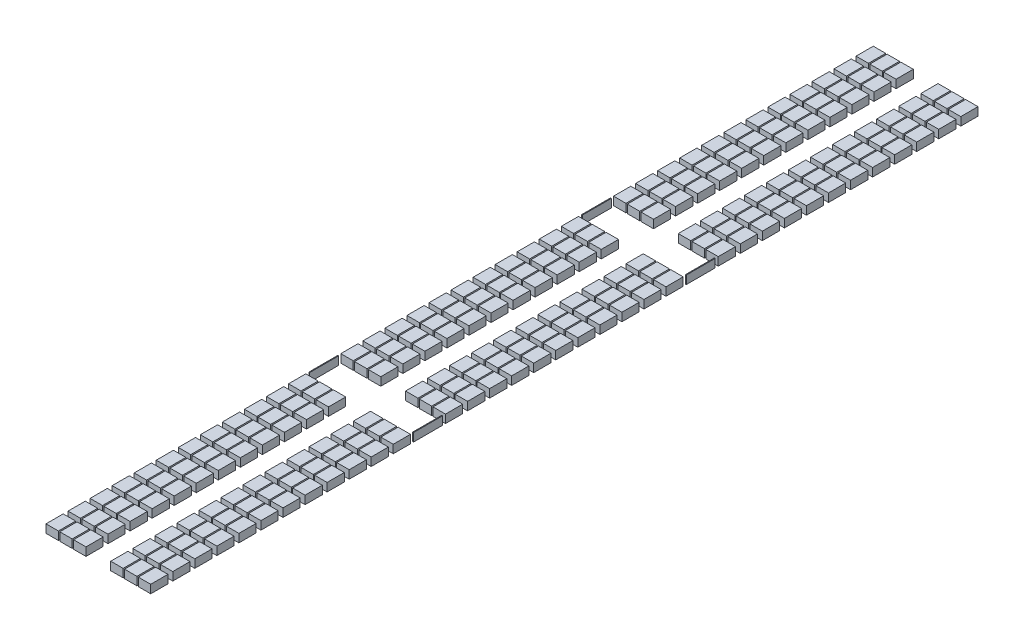
SolidWorks part; units mm, degrees
ref_plane "Front Plane" through (0, 0, 0) normal (0, 0, 1) x (1, 0, 0)
ref_plane "Top Plane" through (0, 0, 0) normal (0, 1, 0) x (1, 0, 0)
ref_plane "Right Plane" through (0, 0, 0) normal (1, 0, 0) x (0, 0, -1)
sketch "Sketch1" plane through (0, 0, 0) normal (0, 1, 0) x (1, 0, 0)
  line L0 (1993.392, 0) -> (-1993.392, 0) construction
  line L1 (1993.392, -15290.8) -> (-1993.392, -15290.8) construction
  line L2 (1993.392, -15290.8) -> (1993.392, 15290.8) construction
  line L3 (1993.392, 15290.8) -> (-1993.392, 15290.8) construction
  line L4 (-1993.392, -15290.8) -> (-1993.392, 15290.8) construction
  line L5 (-1993.392, 5630.3333) -> (1993.392, 5630.3333) construction
  line L6 (-1993.392, 4563.5333) -> (1993.392, 4563.5333) construction
  line L11 (0, -15290.8) -> (0, 15290.8) construction
  line L12 (-1993.392, -4563.5333) -> (1993.392, -4563.5333) construction
  line L13 (-1993.392, -5630.3333) -> (1993.392, -5630.3333) construction
  line L14 (-1421.892, -14613.4667) -> (-964.692, -14613.4667)
  line L15 (-1929.892, -14613.4667) -> (-1472.692, -14613.4667)
  line L16 (-1929.892, -14613.4667) -> (-1929.892, -15248.4667)
  line L17 (-1929.892, -15248.4667) -> (-1472.692, -15248.4667)
  line L18 (-1472.692, -14613.4667) -> (-1472.692, -15248.4667)
  line L19 (-1421.892, -14613.4667) -> (-1421.892, -15248.4667)
  line L20 (-1421.892, -15248.4667) -> (-964.692, -15248.4667)
  line L21 (-964.692, -14613.4667) -> (-964.692, -15248.4667)
  line L22 (-913.892, -14613.4667) -> (-456.692, -14613.4667)
  line L23 (-913.892, -14613.4667) -> (-913.892, -15248.4667)
  line L24 (-913.892, -15248.4667) -> (-456.692, -15248.4667)
  line L25 (-456.692, -14613.4667) -> (-456.692, -15248.4667)
  line L26 (-1421.892, -13800.6667) -> (-964.692, -13800.6667)
  line L27 (-1421.892, -13800.6667) -> (-1421.892, -14435.6667)
  line L28 (-1421.892, -14435.6667) -> (-964.692, -14435.6667)
  line L29 (-964.692, -13800.6667) -> (-964.692, -14435.6667)
  line L30 (-913.892, -13800.6667) -> (-456.692, -13800.6667)
  line L31 (-913.892, -13800.6667) -> (-913.892, -14435.6667)
  line L32 (-913.892, -14435.6667) -> (-456.692, -14435.6667)
  line L33 (-456.692, -13800.6667) -> (-456.692, -14435.6667)
  line L34 (-1421.892, -12987.8667) -> (-964.692, -12987.8667)
  line L35 (-1421.892, -12987.8667) -> (-1421.892, -13622.8667)
  line L36 (-1421.892, -13622.8667) -> (-964.692, -13622.8667)
  line L37 (-964.692, -12987.8667) -> (-964.692, -13622.8667)
  line L38 (-913.892, -12987.8667) -> (-456.692, -12987.8667)
  line L39 (-913.892, -12987.8667) -> (-913.892, -13622.8667)
  line L40 (-913.892, -13622.8667) -> (-456.692, -13622.8667)
  line L41 (-456.692, -12987.8667) -> (-456.692, -13622.8667)
  line L42 (-1929.892, -13800.6667) -> (-1472.692, -13800.6667)
  line L43 (-1929.892, -13800.6667) -> (-1929.892, -14435.6667)
  line L44 (-1929.892, -14435.6667) -> (-1472.692, -14435.6667)
  line L45 (-1472.692, -13800.6667) -> (-1472.692, -14435.6667)
  line L46 (-1929.892, -12987.8667) -> (-1472.692, -12987.8667)
  line L47 (-1929.892, -12987.8667) -> (-1929.892, -13622.8667)
  line L48 (-1929.892, -13622.8667) -> (-1472.692, -13622.8667)
  line L49 (-1472.692, -12987.8667) -> (-1472.692, -13622.8667)
  line L50 (-1929.892, -12175.0667) -> (-1472.692, -12175.0667)
  line L51 (-1929.892, -12175.0667) -> (-1929.892, -12810.0667)
  line L52 (-1929.892, -12810.0667) -> (-1472.692, -12810.0667)
  line L53 (-1472.692, -12175.0667) -> (-1472.692, -12810.0667)
  line L54 (-1421.892, -12175.0667) -> (-964.692, -12175.0667)
  line L55 (-1421.892, -12175.0667) -> (-1421.892, -12810.0667)
  line L56 (-1421.892, -12810.0667) -> (-964.692, -12810.0667)
  line L57 (-964.692, -12175.0667) -> (-964.692, -12810.0667)
  line L58 (-913.892, -12175.0667) -> (-456.692, -12175.0667)
  line L59 (-913.892, -12175.0667) -> (-913.892, -12810.0667)
  line L60 (-913.892, -12810.0667) -> (-456.692, -12810.0667)
  line L61 (-456.692, -12175.0667) -> (-456.692, -12810.0667)
  line L62 (-1929.892, -11362.2667) -> (-1472.692, -11362.2667)
  line L63 (-1929.892, -11362.2667) -> (-1929.892, -11997.2667)
  line L64 (-1929.892, -11997.2667) -> (-1472.692, -11997.2667)
  line L65 (-1472.692, -11362.2667) -> (-1472.692, -11997.2667)
  line L66 (-1421.892, -11362.2667) -> (-964.692, -11362.2667)
  line L67 (-1421.892, -11362.2667) -> (-1421.892, -11997.2667)
  line L68 (-1421.892, -11997.2667) -> (-964.692, -11997.2667)
  line L69 (-964.692, -11362.2667) -> (-964.692, -11997.2667)
  line L70 (-913.892, -11362.2667) -> (-456.692, -11362.2667)
  line L71 (-913.892, -11362.2667) -> (-913.892, -11997.2667)
  line L72 (-913.892, -11997.2667) -> (-456.692, -11997.2667)
  line L73 (-456.692, -11362.2667) -> (-456.692, -11997.2667)
  line L74 (-1929.892, -10549.4667) -> (-1472.692, -10549.4667)
  line L75 (-1929.892, -10549.4667) -> (-1929.892, -11184.4667)
  line L76 (-1929.892, -11184.4667) -> (-1472.692, -11184.4667)
  line L77 (-1472.692, -10549.4667) -> (-1472.692, -11184.4667)
  line L78 (-1421.892, -10549.4667) -> (-964.692, -10549.4667)
  line L79 (-1421.892, -10549.4667) -> (-1421.892, -11184.4667)
  line L80 (-1421.892, -11184.4667) -> (-964.692, -11184.4667)
  line L81 (-964.692, -10549.4667) -> (-964.692, -11184.4667)
  line L82 (-913.892, -10549.4667) -> (-456.692, -10549.4667)
  line L83 (-913.892, -10549.4667) -> (-913.892, -11184.4667)
  line L84 (-913.892, -11184.4667) -> (-456.692, -11184.4667)
  line L85 (-456.692, -10549.4667) -> (-456.692, -11184.4667)
  line L86 (-1929.892, -9736.6667) -> (-1472.692, -9736.6667)
  line L87 (-1929.892, -9736.6667) -> (-1929.892, -10371.6667)
  line L88 (-1929.892, -10371.6667) -> (-1472.692, -10371.6667)
  line L89 (-1472.692, -9736.6667) -> (-1472.692, -10371.6667)
  line L90 (-1421.892, -9736.6667) -> (-964.692, -9736.6667)
  line L91 (-1421.892, -9736.6667) -> (-1421.892, -10371.6667)
  line L92 (-1421.892, -10371.6667) -> (-964.692, -10371.6667)
  line L93 (-964.692, -9736.6667) -> (-964.692, -10371.6667)
  line L94 (-913.892, -9736.6667) -> (-456.692, -9736.6667)
  line L95 (-913.892, -9736.6667) -> (-913.892, -10371.6667)
  line L96 (-913.892, -10371.6667) -> (-456.692, -10371.6667)
  line L97 (-456.692, -9736.6667) -> (-456.692, -10371.6667)
  line L98 (-1929.892, -8923.8667) -> (-1472.692, -8923.8667)
  line L99 (-1929.892, -8923.8667) -> (-1929.892, -9558.8667)
  line L100 (-1929.892, -9558.8667) -> (-1472.692, -9558.8667)
  line L101 (-1472.692, -8923.8667) -> (-1472.692, -9558.8667)
  line L102 (-1421.892, -8923.8667) -> (-964.692, -8923.8667)
  line L103 (-1421.892, -8923.8667) -> (-1421.892, -9558.8667)
  line L104 (-1421.892, -9558.8667) -> (-964.692, -9558.8667)
  line L105 (-964.692, -8923.8667) -> (-964.692, -9558.8667)
  line L106 (-913.892, -8923.8667) -> (-456.692, -8923.8667)
  line L107 (-913.892, -8923.8667) -> (-913.892, -9558.8667)
  line L108 (-913.892, -9558.8667) -> (-456.692, -9558.8667)
  line L109 (-456.692, -8923.8667) -> (-456.692, -9558.8667)
  line L110 (-1929.892, -8111.0667) -> (-1472.692, -8111.0667)
  line L111 (-1929.892, -8111.0667) -> (-1929.892, -8746.0667)
  line L112 (-1929.892, -8746.0667) -> (-1472.692, -8746.0667)
  line L113 (-1472.692, -8111.0667) -> (-1472.692, -8746.0667)
  line L114 (-1421.892, -8111.0667) -> (-964.692, -8111.0667)
  line L115 (-1421.892, -8111.0667) -> (-1421.892, -8746.0667)
  line L116 (-1421.892, -8746.0667) -> (-964.692, -8746.0667)
  line L117 (-964.692, -8111.0667) -> (-964.692, -8746.0667)
  line L118 (-913.892, -8111.0667) -> (-456.692, -8111.0667)
  line L119 (-913.892, -8111.0667) -> (-913.892, -8746.0667)
  line L120 (-913.892, -8746.0667) -> (-456.692, -8746.0667)
  line L121 (-456.692, -8111.0667) -> (-456.692, -8746.0667)
  line L122 (-1929.892, -7298.2667) -> (-1472.692, -7298.2667)
  line L123 (-1929.892, -7298.2667) -> (-1929.892, -7933.2667)
  line L124 (-1929.892, -7933.2667) -> (-1472.692, -7933.2667)
  line L125 (-1472.692, -7298.2667) -> (-1472.692, -7933.2667)
  line L126 (-1421.892, -7298.2667) -> (-964.692, -7298.2667)
  line L127 (-1421.892, -7298.2667) -> (-1421.892, -7933.2667)
  line L128 (-1421.892, -7933.2667) -> (-964.692, -7933.2667)
  line L129 (-964.692, -7298.2667) -> (-964.692, -7933.2667)
  line L130 (-913.892, -7298.2667) -> (-456.692, -7298.2667)
  line L131 (-913.892, -7298.2667) -> (-913.892, -7933.2667)
  line L132 (-913.892, -7933.2667) -> (-456.692, -7933.2667)
  line L133 (-456.692, -7298.2667) -> (-456.692, -7933.2667)
  line L134 (-1929.892, -6485.4667) -> (-1472.692, -6485.4667)
  line L135 (-1929.892, -6485.4667) -> (-1929.892, -7120.4667)
  line L136 (-1929.892, -7120.4667) -> (-1472.692, -7120.4667)
  line L137 (-1472.692, -6485.4667) -> (-1472.692, -7120.4667)
  line L138 (-1421.892, -6485.4667) -> (-964.692, -6485.4667)
  line L139 (-1421.892, -6485.4667) -> (-1421.892, -7120.4667)
  line L140 (-1421.892, -7120.4667) -> (-964.692, -7120.4667)
  line L141 (-964.692, -6485.4667) -> (-964.692, -7120.4667)
  line L142 (-913.892, -6485.4667) -> (-456.692, -6485.4667)
  line L143 (-913.892, -6485.4667) -> (-913.892, -7120.4667)
  line L144 (-913.892, -7120.4667) -> (-456.692, -7120.4667)
  line L145 (-456.692, -6485.4667) -> (-456.692, -7120.4667)
  line L146 (-1929.892, -5672.6667) -> (-1472.692, -5672.6667)
  line L147 (-1929.892, -5672.6667) -> (-1929.892, -6307.6667)
  line L148 (-1929.892, -6307.6667) -> (-1472.692, -6307.6667)
  line L149 (-1472.692, -5672.6667) -> (-1472.692, -6307.6667)
  line L150 (-1421.892, -5672.6667) -> (-964.692, -5672.6667)
  line L151 (-1421.892, -5672.6667) -> (-1421.892, -6307.6667)
  line L152 (-1421.892, -6307.6667) -> (-964.692, -6307.6667)
  line L153 (-964.692, -5672.6667) -> (-964.692, -6307.6667)
  line L154 (-913.892, -5672.6667) -> (-456.692, -5672.6667)
  line L155 (-913.892, -5672.6667) -> (-913.892, -6307.6667)
  line L156 (-913.892, -6307.6667) -> (-456.692, -6307.6667)
  line L157 (-456.692, -5672.6667) -> (-456.692, -6307.6667)
  line L158 (-456.692, -5672.6667) -> (-456.692, -15248.4667) construction
  line L159 (-456.692, -10460.5667) -> (2544.9668, -10460.5667) construction
  line L160 (-1929.892, -3746.5) -> (-1472.692, -3746.5)
  line L161 (-1929.892, -3746.5) -> (-1929.892, -4381.5)
  line L162 (-1929.892, -4381.5) -> (-1472.692, -4381.5)
  line L163 (-1472.692, -3746.5) -> (-1472.692, -4381.5)
  line L164 (-1421.892, -3746.5) -> (-964.692, -3746.5)
  line L165 (-1421.892, -3746.5) -> (-1421.892, -4381.5)
  line L166 (-1421.892, -4381.5) -> (-964.692, -4381.5)
  line L167 (-964.692, -3746.5) -> (-964.692, -4381.5)
  line L168 (-913.892, -3746.5) -> (-456.692, -3746.5)
  line L169 (-913.892, -3746.5) -> (-913.892, -4381.5)
  line L170 (-913.892, -4381.5) -> (-456.692, -4381.5)
  line L171 (-456.692, -3746.5) -> (-456.692, -4381.5)
  line L172 (-1421.892, -2933.7) -> (-964.692, -2933.7)
  line L173 (-1421.892, -2933.7) -> (-1421.892, -3568.7)
  line L174 (-1421.892, -3568.7) -> (-964.692, -3568.7)
  line L175 (-964.692, -2933.7) -> (-964.692, -3568.7)
  line L176 (-913.892, -2933.7) -> (-456.692, -2933.7)
  line L177 (-913.892, -2933.7) -> (-913.892, -3568.7)
  line L178 (-913.892, -3568.7) -> (-456.692, -3568.7)
  line L179 (-456.692, -2933.7) -> (-456.692, -3568.7)
  line L180 (-1421.892, -2120.9) -> (-964.692, -2120.9)
  line L181 (-1421.892, -2120.9) -> (-1421.892, -2755.9)
  line L182 (-1421.892, -2755.9) -> (-964.692, -2755.9)
  line L183 (-964.692, -2120.9) -> (-964.692, -2755.9)
  line L184 (-913.892, -2120.9) -> (-456.692, -2120.9)
  line L185 (-913.892, -2120.9) -> (-913.892, -2755.9)
  line L186 (-913.892, -2755.9) -> (-456.692, -2755.9)
  line L187 (-456.692, -2120.9) -> (-456.692, -2755.9)
  line L188 (-1421.892, -1308.1) -> (-964.692, -1308.1)
  line L189 (-1421.892, -1308.1) -> (-1421.892, -1943.1)
  line L190 (-1421.892, -1943.1) -> (-964.692, -1943.1)
  line L191 (-964.692, -1308.1) -> (-964.692, -1943.1)
  line L192 (-913.892, -1308.1) -> (-456.692, -1308.1)
  line L193 (-913.892, -1308.1) -> (-913.892, -1943.1)
  line L194 (-913.892, -1943.1) -> (-456.692, -1943.1)
  line L195 (-456.692, -1308.1) -> (-456.692, -1943.1)
  line L196 (-1421.892, -495.3) -> (-964.692, -495.3)
  line L197 (-1421.892, -495.3) -> (-1421.892, -1130.3)
  line L198 (-1421.892, -1130.3) -> (-964.692, -1130.3)
  line L199 (-964.692, -495.3) -> (-964.692, -1130.3)
  line L200 (-913.892, -495.3) -> (-456.692, -495.3)
  line L201 (-913.892, -495.3) -> (-913.892, -1130.3)
  line L202 (-913.892, -1130.3) -> (-456.692, -1130.3)
  line L203 (-456.692, -495.3) -> (-456.692, -1130.3)
  line L204 (-1929.892, -2933.7) -> (-1472.692, -2933.7)
  line L205 (-1929.892, -2933.7) -> (-1929.892, -3568.7)
  line L206 (-1929.892, -3568.7) -> (-1472.692, -3568.7)
  line L207 (-1472.692, -2933.7) -> (-1472.692, -3568.7)
  line L208 (-1929.892, -2120.9) -> (-1472.692, -2120.9)
  line L209 (-1929.892, -2120.9) -> (-1929.892, -2755.9)
  line L210 (-1929.892, -2755.9) -> (-1472.692, -2755.9)
  line L211 (-1472.692, -2120.9) -> (-1472.692, -2755.9)
  line L212 (-1929.892, -1308.1) -> (-1472.692, -1308.1)
  line L213 (-1929.892, -1308.1) -> (-1929.892, -1943.1)
  line L214 (-1929.892, -1943.1) -> (-1472.692, -1943.1)
  line L215 (-1472.692, -1308.1) -> (-1472.692, -1943.1)
  line L216 (-1929.892, -495.3) -> (-1472.692, -495.3)
  line L217 (-1929.892, -495.3) -> (-1929.892, -1130.3)
  line L218 (-1929.892, -1130.3) -> (-1472.692, -1130.3)
  line L219 (-1472.692, -495.3) -> (-1472.692, -1130.3)
  line L220 (-1929.892, 317.5) -> (-1472.692, 317.5)
  line L221 (-1929.892, 317.5) -> (-1929.892, -317.5)
  line L222 (-1929.892, -317.5) -> (-1472.692, -317.5)
  line L223 (-1472.692, 317.5) -> (-1472.692, -317.5)
  line L224 (-1421.892, 317.5) -> (-964.692, 317.5)
  line L225 (-1421.892, 317.5) -> (-1421.892, -317.5)
  line L226 (-1421.892, -317.5) -> (-964.692, -317.5)
  line L227 (-964.692, 317.5) -> (-964.692, -317.5)
  line L228 (-913.892, 317.5) -> (-456.692, 317.5)
  line L229 (-913.892, 317.5) -> (-913.892, -317.5)
  line L230 (-913.892, -317.5) -> (-456.692, -317.5)
  line L231 (-456.692, 317.5) -> (-456.692, -317.5)
  line L232 (-1929.892, 1130.3) -> (-1472.692, 1130.3)
  line L233 (-1929.892, 1130.3) -> (-1929.892, 495.3)
  line L234 (-1929.892, 495.3) -> (-1472.692, 495.3)
  line L235 (-1472.692, 1130.3) -> (-1472.692, 495.3)
  line L236 (-1421.892, 1130.3) -> (-964.692, 1130.3)
  line L237 (-1421.892, 1130.3) -> (-1421.892, 495.3)
  line L238 (-1421.892, 495.3) -> (-964.692, 495.3)
  line L239 (-964.692, 1130.3) -> (-964.692, 495.3)
  line L240 (-913.892, 1130.3) -> (-456.692, 1130.3)
  line L241 (-913.892, 1130.3) -> (-913.892, 495.3)
  line L242 (-913.892, 495.3) -> (-456.692, 495.3)
  line L243 (-456.692, 1130.3) -> (-456.692, 495.3)
  line L244 (-1929.892, 1943.1) -> (-1472.692, 1943.1)
  line L245 (-1929.892, 1943.1) -> (-1929.892, 1308.1)
  line L246 (-1929.892, 1308.1) -> (-1472.692, 1308.1)
  line L247 (-1472.692, 1943.1) -> (-1472.692, 1308.1)
  line L248 (-1421.892, 1943.1) -> (-964.692, 1943.1)
  line L249 (-1421.892, 1943.1) -> (-1421.892, 1308.1)
  line L250 (-1421.892, 1308.1) -> (-964.692, 1308.1)
  line L251 (-964.692, 1943.1) -> (-964.692, 1308.1)
  line L252 (-913.892, 1943.1) -> (-456.692, 1943.1)
  line L253 (-913.892, 1943.1) -> (-913.892, 1308.1)
  line L254 (-913.892, 1308.1) -> (-456.692, 1308.1)
  line L255 (-456.692, 1943.1) -> (-456.692, 1308.1)
  line L256 (-1929.892, 2755.9) -> (-1472.692, 2755.9)
  line L257 (-1929.892, 2755.9) -> (-1929.892, 2120.9)
  line L258 (-1929.892, 2120.9) -> (-1472.692, 2120.9)
  line L259 (-1472.692, 2755.9) -> (-1472.692, 2120.9)
  line L260 (-1421.892, 2755.9) -> (-964.692, 2755.9)
  line L261 (-1421.892, 2755.9) -> (-1421.892, 2120.9)
  line L262 (-1421.892, 2120.9) -> (-964.692, 2120.9)
  line L263 (-964.692, 2755.9) -> (-964.692, 2120.9)
  line L264 (-913.892, 2755.9) -> (-456.692, 2755.9)
  line L265 (-913.892, 2755.9) -> (-913.892, 2120.9)
  line L266 (-913.892, 2120.9) -> (-456.692, 2120.9)
  line L267 (-456.692, 2755.9) -> (-456.692, 2120.9)
  line L268 (-1929.892, 3568.7) -> (-1472.692, 3568.7)
  line L269 (-1929.892, 3568.7) -> (-1929.892, 2933.7)
  line L270 (-1929.892, 2933.7) -> (-1472.692, 2933.7)
  line L271 (-1472.692, 3568.7) -> (-1472.692, 2933.7)
  line L272 (-1421.892, 3568.7) -> (-964.692, 3568.7)
  line L273 (-1421.892, 3568.7) -> (-1421.892, 2933.7)
  line L274 (-1421.892, 2933.7) -> (-964.692, 2933.7)
  line L275 (-964.692, 3568.7) -> (-964.692, 2933.7)
  line L276 (-913.892, 3568.7) -> (-456.692, 3568.7)
  line L277 (-913.892, 3568.7) -> (-913.892, 2933.7)
  line L278 (-913.892, 2933.7) -> (-456.692, 2933.7)
  line L279 (-456.692, 3568.7) -> (-456.692, 2933.7)
  line L280 (-1929.892, 4381.5) -> (-1472.692, 4381.5)
  line L281 (-1929.892, 4381.5) -> (-1929.892, 3746.5)
  line L282 (-1929.892, 3746.5) -> (-1472.692, 3746.5)
  line L283 (-1472.692, 4381.5) -> (-1472.692, 3746.5)
  line L284 (-1421.892, 4381.5) -> (-964.692, 4381.5)
  line L285 (-1421.892, 4381.5) -> (-1421.892, 3746.5)
  line L286 (-1421.892, 3746.5) -> (-964.692, 3746.5)
  line L287 (-964.692, 4381.5) -> (-964.692, 3746.5)
  line L288 (-913.892, 4381.5) -> (-456.692, 4381.5)
  line L289 (-913.892, 4381.5) -> (-913.892, 3746.5)
  line L290 (-913.892, 3746.5) -> (-456.692, 3746.5)
  line L291 (-456.692, 4381.5) -> (-456.692, 3746.5)
  line L292 (-456.692, 4381.5) -> (-456.692, -4381.5) construction
  line L293 (-913.892, 15248.4667) -> (-456.692, 15248.4667)
  line L294 (-1421.892, 15248.4667) -> (-964.692, 15248.4667)
  line L295 (-1929.892, 15248.4667) -> (-1472.692, 15248.4667)
  line L296 (-913.892, 5672.6667) -> (-456.692, 5672.6667)
  line L297 (-1421.892, 5672.6667) -> (-964.692, 5672.6667)
  line L298 (-1929.892, 5672.6667) -> (-1472.692, 5672.6667)
  line L299 (-456.692, 10460.5667) -> (2544.9668, 10460.5667) construction
  line L300 (-456.692, 5672.6667) -> (-456.692, 15248.4667) construction
  line L301 (-456.692, 5672.6667) -> (-456.692, 6307.6667)
  line L302 (-913.892, 6307.6667) -> (-456.692, 6307.6667)
  line L303 (-913.892, 5672.6667) -> (-913.892, 6307.6667)
  line L304 (-964.692, 5672.6667) -> (-964.692, 6307.6667)
  line L305 (-1421.892, 6307.6667) -> (-964.692, 6307.6667)
  line L306 (-1421.892, 5672.6667) -> (-1421.892, 6307.6667)
  line L307 (-1472.692, 5672.6667) -> (-1472.692, 6307.6667)
  line L308 (-1929.892, 6307.6667) -> (-1472.692, 6307.6667)
  line L309 (-1929.892, 5672.6667) -> (-1929.892, 6307.6667)
  line L310 (-456.692, 6485.4667) -> (-456.692, 7120.4667)
  line L311 (-913.892, 7120.4667) -> (-456.692, 7120.4667)
  line L312 (-913.892, 6485.4667) -> (-913.892, 7120.4667)
  line L313 (-913.892, 6485.4667) -> (-456.692, 6485.4667)
  line L314 (-964.692, 6485.4667) -> (-964.692, 7120.4667)
  line L315 (-1421.892, 7120.4667) -> (-964.692, 7120.4667)
  line L316 (-1421.892, 6485.4667) -> (-1421.892, 7120.4667)
  line L317 (-1421.892, 6485.4667) -> (-964.692, 6485.4667)
  line L318 (-1472.692, 6485.4667) -> (-1472.692, 7120.4667)
  line L319 (-1929.892, 7120.4667) -> (-1472.692, 7120.4667)
  line L320 (-1929.892, 6485.4667) -> (-1929.892, 7120.4667)
  line L321 (-1929.892, 6485.4667) -> (-1472.692, 6485.4667)
  line L322 (-456.692, 7298.2667) -> (-456.692, 7933.2667)
  line L323 (-913.892, 7933.2667) -> (-456.692, 7933.2667)
  line L324 (-913.892, 7298.2667) -> (-913.892, 7933.2667)
  line L325 (-913.892, 7298.2667) -> (-456.692, 7298.2667)
  line L326 (-964.692, 7298.2667) -> (-964.692, 7933.2667)
  line L327 (-1421.892, 7933.2667) -> (-964.692, 7933.2667)
  line L328 (-1421.892, 7298.2667) -> (-1421.892, 7933.2667)
  line L329 (-1421.892, 7298.2667) -> (-964.692, 7298.2667)
  line L330 (-1472.692, 7298.2667) -> (-1472.692, 7933.2667)
  line L331 (-1929.892, 7933.2667) -> (-1472.692, 7933.2667)
  line L332 (-1929.892, 7298.2667) -> (-1929.892, 7933.2667)
  line L333 (-1929.892, 7298.2667) -> (-1472.692, 7298.2667)
  line L334 (-456.692, 8111.0667) -> (-456.692, 8746.0667)
  line L335 (-913.892, 8746.0667) -> (-456.692, 8746.0667)
  line L336 (-913.892, 8111.0667) -> (-913.892, 8746.0667)
  line L337 (-913.892, 8111.0667) -> (-456.692, 8111.0667)
  line L338 (-964.692, 8111.0667) -> (-964.692, 8746.0667)
  line L339 (-1421.892, 8746.0667) -> (-964.692, 8746.0667)
  line L340 (-1421.892, 8111.0667) -> (-1421.892, 8746.0667)
  line L341 (-1421.892, 8111.0667) -> (-964.692, 8111.0667)
  line L342 (-1472.692, 8111.0667) -> (-1472.692, 8746.0667)
  line L343 (-1929.892, 8746.0667) -> (-1472.692, 8746.0667)
  line L344 (-1929.892, 8111.0667) -> (-1929.892, 8746.0667)
  line L345 (-1929.892, 8111.0667) -> (-1472.692, 8111.0667)
  line L346 (-456.692, 8923.8667) -> (-456.692, 9558.8667)
  line L347 (-913.892, 9558.8667) -> (-456.692, 9558.8667)
  line L348 (-913.892, 8923.8667) -> (-913.892, 9558.8667)
  line L349 (-913.892, 8923.8667) -> (-456.692, 8923.8667)
  line L350 (-964.692, 8923.8667) -> (-964.692, 9558.8667)
  line L351 (-1421.892, 9558.8667) -> (-964.692, 9558.8667)
  line L352 (-1421.892, 8923.8667) -> (-1421.892, 9558.8667)
  line L353 (-1421.892, 8923.8667) -> (-964.692, 8923.8667)
  line L354 (-1472.692, 8923.8667) -> (-1472.692, 9558.8667)
  line L355 (-1929.892, 9558.8667) -> (-1472.692, 9558.8667)
  line L356 (-1929.892, 8923.8667) -> (-1929.892, 9558.8667)
  line L357 (-1929.892, 8923.8667) -> (-1472.692, 8923.8667)
  line L358 (-456.692, 9736.6667) -> (-456.692, 10371.6667)
  line L359 (-913.892, 10371.6667) -> (-456.692, 10371.6667)
  line L360 (-913.892, 9736.6667) -> (-913.892, 10371.6667)
  line L361 (-913.892, 9736.6667) -> (-456.692, 9736.6667)
  line L362 (-964.692, 9736.6667) -> (-964.692, 10371.6667)
  line L363 (-1421.892, 10371.6667) -> (-964.692, 10371.6667)
  line L364 (-1421.892, 9736.6667) -> (-1421.892, 10371.6667)
  line L365 (-1421.892, 9736.6667) -> (-964.692, 9736.6667)
  line L366 (-1472.692, 9736.6667) -> (-1472.692, 10371.6667)
  line L367 (-1929.892, 10371.6667) -> (-1472.692, 10371.6667)
  line L368 (-1929.892, 9736.6667) -> (-1929.892, 10371.6667)
  line L369 (-1929.892, 9736.6667) -> (-1472.692, 9736.6667)
  line L370 (-456.692, 10549.4667) -> (-456.692, 11184.4667)
  line L371 (-913.892, 11184.4667) -> (-456.692, 11184.4667)
  line L372 (-913.892, 10549.4667) -> (-913.892, 11184.4667)
  line L373 (-913.892, 10549.4667) -> (-456.692, 10549.4667)
  line L374 (-964.692, 10549.4667) -> (-964.692, 11184.4667)
  line L375 (-1421.892, 11184.4667) -> (-964.692, 11184.4667)
  line L376 (-1421.892, 10549.4667) -> (-1421.892, 11184.4667)
  line L377 (-1421.892, 10549.4667) -> (-964.692, 10549.4667)
  line L378 (-1472.692, 10549.4667) -> (-1472.692, 11184.4667)
  line L379 (-1929.892, 11184.4667) -> (-1472.692, 11184.4667)
  line L380 (-1929.892, 10549.4667) -> (-1929.892, 11184.4667)
  line L381 (-1929.892, 10549.4667) -> (-1472.692, 10549.4667)
  line L382 (-456.692, 11362.2667) -> (-456.692, 11997.2667)
  line L383 (-913.892, 11997.2667) -> (-456.692, 11997.2667)
  line L384 (-913.892, 11362.2667) -> (-913.892, 11997.2667)
  line L385 (-913.892, 11362.2667) -> (-456.692, 11362.2667)
  line L386 (-964.692, 11362.2667) -> (-964.692, 11997.2667)
  line L387 (-1421.892, 11997.2667) -> (-964.692, 11997.2667)
  line L388 (-1421.892, 11362.2667) -> (-1421.892, 11997.2667)
  line L389 (-1421.892, 11362.2667) -> (-964.692, 11362.2667)
  line L390 (-1472.692, 11362.2667) -> (-1472.692, 11997.2667)
  line L391 (-1929.892, 11997.2667) -> (-1472.692, 11997.2667)
  line L392 (-1929.892, 11362.2667) -> (-1929.892, 11997.2667)
  line L393 (-1929.892, 11362.2667) -> (-1472.692, 11362.2667)
  line L394 (-456.692, 12175.0667) -> (-456.692, 12810.0667)
  line L395 (-913.892, 12810.0667) -> (-456.692, 12810.0667)
  line L396 (-913.892, 12175.0667) -> (-913.892, 12810.0667)
  line L397 (-913.892, 12175.0667) -> (-456.692, 12175.0667)
  line L398 (-964.692, 12175.0667) -> (-964.692, 12810.0667)
  line L399 (-1421.892, 12810.0667) -> (-964.692, 12810.0667)
  line L400 (-1421.892, 12175.0667) -> (-1421.892, 12810.0667)
  line L401 (-1421.892, 12175.0667) -> (-964.692, 12175.0667)
  line L402 (-1472.692, 12175.0667) -> (-1472.692, 12810.0667)
  line L403 (-1929.892, 12810.0667) -> (-1472.692, 12810.0667)
  line L404 (-1929.892, 12175.0667) -> (-1929.892, 12810.0667)
  line L405 (-1929.892, 12175.0667) -> (-1472.692, 12175.0667)
  line L406 (-1472.692, 12987.8667) -> (-1472.692, 13622.8667)
  line L407 (-1929.892, 13622.8667) -> (-1472.692, 13622.8667)
  line L408 (-1929.892, 12987.8667) -> (-1929.892, 13622.8667)
  line L409 (-1929.892, 12987.8667) -> (-1472.692, 12987.8667)
  line L410 (-1472.692, 13800.6667) -> (-1472.692, 14435.6667)
  line L411 (-1929.892, 14435.6667) -> (-1472.692, 14435.6667)
  line L412 (-1929.892, 13800.6667) -> (-1929.892, 14435.6667)
  line L413 (-1929.892, 13800.6667) -> (-1472.692, 13800.6667)
  line L414 (-456.692, 12987.8667) -> (-456.692, 13622.8667)
  line L415 (-913.892, 13622.8667) -> (-456.692, 13622.8667)
  line L416 (-913.892, 12987.8667) -> (-913.892, 13622.8667)
  line L417 (-913.892, 12987.8667) -> (-456.692, 12987.8667)
  line L418 (-964.692, 12987.8667) -> (-964.692, 13622.8667)
  line L419 (-1421.892, 13622.8667) -> (-964.692, 13622.8667)
  line L420 (-1421.892, 12987.8667) -> (-1421.892, 13622.8667)
  line L421 (-1421.892, 12987.8667) -> (-964.692, 12987.8667)
  line L422 (-456.692, 13800.6667) -> (-456.692, 14435.6667)
  line L423 (-913.892, 14435.6667) -> (-456.692, 14435.6667)
  line L424 (-913.892, 13800.6667) -> (-913.892, 14435.6667)
  line L425 (-913.892, 13800.6667) -> (-456.692, 13800.6667)
  line L426 (-964.692, 13800.6667) -> (-964.692, 14435.6667)
  line L427 (-1421.892, 14435.6667) -> (-964.692, 14435.6667)
  line L428 (-1421.892, 13800.6667) -> (-1421.892, 14435.6667)
  line L429 (-1421.892, 13800.6667) -> (-964.692, 13800.6667)
  line L430 (-456.692, 14613.4667) -> (-456.692, 15248.4667)
  line L431 (-913.892, 14613.4667) -> (-913.892, 15248.4667)
  line L432 (-913.892, 14613.4667) -> (-456.692, 14613.4667)
  line L433 (-964.692, 14613.4667) -> (-964.692, 15248.4667)
  line L434 (-1421.892, 14613.4667) -> (-1421.892, 15248.4667)
  line L435 (-1472.692, 14613.4667) -> (-1472.692, 15248.4667)
  line L436 (-1929.892, 14613.4667) -> (-1929.892, 15248.4667)
  line L437 (-1929.892, 14613.4667) -> (-1472.692, 14613.4667)
  line L438 (-1421.892, 14613.4667) -> (-964.692, 14613.4667)
  line L439 (456.692, 5672.6667) -> (456.692, 15248.4667) construction
  line L440 (456.692, 4381.5) -> (456.692, -4381.5) construction
  line L441 (456.692, -5672.6667) -> (456.692, -15248.4667) construction
  line L442 (1421.892, 14613.4667) -> (964.692, 14613.4667)
  line L443 (1929.892, 14613.4667) -> (1472.692, 14613.4667)
  line L444 (1929.892, 14613.4667) -> (1929.892, 15248.4667)
  line L445 (1472.692, 14613.4667) -> (1472.692, 15248.4667)
  line L446 (1421.892, 14613.4667) -> (1421.892, 15248.4667)
  line L447 (964.692, 14613.4667) -> (964.692, 15248.4667)
  line L448 (913.892, 14613.4667) -> (456.692, 14613.4667)
  line L449 (913.892, 14613.4667) -> (913.892, 15248.4667)
  line L450 (456.692, 14613.4667) -> (456.692, 15248.4667)
  line L451 (1421.892, 13800.6667) -> (964.692, 13800.6667)
  line L452 (1421.892, 13800.6667) -> (1421.892, 14435.6667)
  line L453 (1421.892, 14435.6667) -> (964.692, 14435.6667)
  line L454 (964.692, 13800.6667) -> (964.692, 14435.6667)
  line L455 (913.892, 13800.6667) -> (456.692, 13800.6667)
  line L456 (913.892, 13800.6667) -> (913.892, 14435.6667)
  line L457 (913.892, 14435.6667) -> (456.692, 14435.6667)
  line L458 (456.692, 13800.6667) -> (456.692, 14435.6667)
  line L459 (1421.892, 12987.8667) -> (964.692, 12987.8667)
  line L460 (1421.892, 12987.8667) -> (1421.892, 13622.8667)
  line L461 (1421.892, 13622.8667) -> (964.692, 13622.8667)
  line L462 (964.692, 12987.8667) -> (964.692, 13622.8667)
  line L463 (913.892, 12987.8667) -> (456.692, 12987.8667)
  line L464 (913.892, 12987.8667) -> (913.892, 13622.8667)
  line L465 (913.892, 13622.8667) -> (456.692, 13622.8667)
  line L466 (456.692, 12987.8667) -> (456.692, 13622.8667)
  line L467 (1929.892, 13800.6667) -> (1472.692, 13800.6667)
  line L468 (1929.892, 13800.6667) -> (1929.892, 14435.6667)
  line L469 (1929.892, 14435.6667) -> (1472.692, 14435.6667)
  line L470 (1472.692, 13800.6667) -> (1472.692, 14435.6667)
  line L471 (1929.892, 12987.8667) -> (1472.692, 12987.8667)
  line L472 (1929.892, 12987.8667) -> (1929.892, 13622.8667)
  line L473 (1929.892, 13622.8667) -> (1472.692, 13622.8667)
  line L474 (1472.692, 12987.8667) -> (1472.692, 13622.8667)
  line L475 (1929.892, 12175.0667) -> (1472.692, 12175.0667)
  line L476 (1929.892, 12175.0667) -> (1929.892, 12810.0667)
  line L477 (1929.892, 12810.0667) -> (1472.692, 12810.0667)
  line L478 (1472.692, 12175.0667) -> (1472.692, 12810.0667)
  line L479 (1421.892, 12175.0667) -> (964.692, 12175.0667)
  line L480 (1421.892, 12175.0667) -> (1421.892, 12810.0667)
  line L481 (1421.892, 12810.0667) -> (964.692, 12810.0667)
  line L482 (964.692, 12175.0667) -> (964.692, 12810.0667)
  line L483 (913.892, 12175.0667) -> (456.692, 12175.0667)
  line L484 (913.892, 12175.0667) -> (913.892, 12810.0667)
  line L485 (913.892, 12810.0667) -> (456.692, 12810.0667)
  line L486 (456.692, 12175.0667) -> (456.692, 12810.0667)
  line L487 (1929.892, 11362.2667) -> (1472.692, 11362.2667)
  line L488 (1929.892, 11362.2667) -> (1929.892, 11997.2667)
  line L489 (1929.892, 11997.2667) -> (1472.692, 11997.2667)
  line L490 (1472.692, 11362.2667) -> (1472.692, 11997.2667)
  line L491 (1421.892, 11362.2667) -> (964.692, 11362.2667)
  line L492 (1421.892, 11362.2667) -> (1421.892, 11997.2667)
  line L493 (1421.892, 11997.2667) -> (964.692, 11997.2667)
  line L494 (964.692, 11362.2667) -> (964.692, 11997.2667)
  line L495 (913.892, 11362.2667) -> (456.692, 11362.2667)
  line L496 (913.892, 11362.2667) -> (913.892, 11997.2667)
  line L497 (913.892, 11997.2667) -> (456.692, 11997.2667)
  line L498 (456.692, 11362.2667) -> (456.692, 11997.2667)
  line L499 (1929.892, 10549.4667) -> (1472.692, 10549.4667)
  line L500 (1929.892, 10549.4667) -> (1929.892, 11184.4667)
  line L501 (1929.892, 11184.4667) -> (1472.692, 11184.4667)
  line L502 (1472.692, 10549.4667) -> (1472.692, 11184.4667)
  line L503 (1421.892, 10549.4667) -> (964.692, 10549.4667)
  line L504 (1421.892, 10549.4667) -> (1421.892, 11184.4667)
  line L505 (1421.892, 11184.4667) -> (964.692, 11184.4667)
  line L506 (964.692, 10549.4667) -> (964.692, 11184.4667)
  line L507 (913.892, 10549.4667) -> (456.692, 10549.4667)
  line L508 (913.892, 10549.4667) -> (913.892, 11184.4667)
  line L509 (913.892, 11184.4667) -> (456.692, 11184.4667)
  line L510 (456.692, 10549.4667) -> (456.692, 11184.4667)
  line L511 (1929.892, 9736.6667) -> (1472.692, 9736.6667)
  line L512 (1929.892, 9736.6667) -> (1929.892, 10371.6667)
  line L513 (1929.892, 10371.6667) -> (1472.692, 10371.6667)
  line L514 (1472.692, 9736.6667) -> (1472.692, 10371.6667)
  line L515 (1421.892, 9736.6667) -> (964.692, 9736.6667)
  line L516 (1421.892, 9736.6667) -> (1421.892, 10371.6667)
  line L517 (1421.892, 10371.6667) -> (964.692, 10371.6667)
  line L518 (964.692, 9736.6667) -> (964.692, 10371.6667)
  line L519 (913.892, 9736.6667) -> (456.692, 9736.6667)
  line L520 (913.892, 9736.6667) -> (913.892, 10371.6667)
  line L521 (913.892, 10371.6667) -> (456.692, 10371.6667)
  line L522 (456.692, 9736.6667) -> (456.692, 10371.6667)
  line L523 (1929.892, 8923.8667) -> (1472.692, 8923.8667)
  line L524 (1929.892, 8923.8667) -> (1929.892, 9558.8667)
  line L525 (1929.892, 9558.8667) -> (1472.692, 9558.8667)
  line L526 (1472.692, 8923.8667) -> (1472.692, 9558.8667)
  line L527 (1421.892, 8923.8667) -> (964.692, 8923.8667)
  line L528 (1421.892, 8923.8667) -> (1421.892, 9558.8667)
  line L529 (1421.892, 9558.8667) -> (964.692, 9558.8667)
  line L530 (964.692, 8923.8667) -> (964.692, 9558.8667)
  line L531 (913.892, 8923.8667) -> (456.692, 8923.8667)
  line L532 (913.892, 8923.8667) -> (913.892, 9558.8667)
  line L533 (913.892, 9558.8667) -> (456.692, 9558.8667)
  line L534 (456.692, 8923.8667) -> (456.692, 9558.8667)
  line L535 (1929.892, 8111.0667) -> (1472.692, 8111.0667)
  line L536 (1929.892, 8111.0667) -> (1929.892, 8746.0667)
  line L537 (1929.892, 8746.0667) -> (1472.692, 8746.0667)
  line L538 (1472.692, 8111.0667) -> (1472.692, 8746.0667)
  line L539 (1421.892, 8111.0667) -> (964.692, 8111.0667)
  line L540 (1421.892, 8111.0667) -> (1421.892, 8746.0667)
  line L541 (1421.892, 8746.0667) -> (964.692, 8746.0667)
  line L542 (964.692, 8111.0667) -> (964.692, 8746.0667)
  line L543 (913.892, 8111.0667) -> (456.692, 8111.0667)
  line L544 (913.892, 8111.0667) -> (913.892, 8746.0667)
  line L545 (913.892, 8746.0667) -> (456.692, 8746.0667)
  line L546 (456.692, 8111.0667) -> (456.692, 8746.0667)
  line L547 (1929.892, 7298.2667) -> (1472.692, 7298.2667)
  line L548 (1929.892, 7298.2667) -> (1929.892, 7933.2667)
  line L549 (1929.892, 7933.2667) -> (1472.692, 7933.2667)
  line L550 (1472.692, 7298.2667) -> (1472.692, 7933.2667)
  line L551 (1421.892, 7298.2667) -> (964.692, 7298.2667)
  line L552 (1421.892, 7298.2667) -> (1421.892, 7933.2667)
  line L553 (1421.892, 7933.2667) -> (964.692, 7933.2667)
  line L554 (964.692, 7298.2667) -> (964.692, 7933.2667)
  line L555 (913.892, 7298.2667) -> (456.692, 7298.2667)
  line L556 (913.892, 7298.2667) -> (913.892, 7933.2667)
  line L557 (913.892, 7933.2667) -> (456.692, 7933.2667)
  line L558 (456.692, 7298.2667) -> (456.692, 7933.2667)
  line L559 (1929.892, 6485.4667) -> (1472.692, 6485.4667)
  line L560 (1929.892, 6485.4667) -> (1929.892, 7120.4667)
  line L561 (1929.892, 7120.4667) -> (1472.692, 7120.4667)
  line L562 (1472.692, 6485.4667) -> (1472.692, 7120.4667)
  line L563 (1421.892, 6485.4667) -> (964.692, 6485.4667)
  line L564 (1421.892, 6485.4667) -> (1421.892, 7120.4667)
  line L565 (1421.892, 7120.4667) -> (964.692, 7120.4667)
  line L566 (964.692, 6485.4667) -> (964.692, 7120.4667)
  line L567 (913.892, 6485.4667) -> (456.692, 6485.4667)
  line L568 (913.892, 6485.4667) -> (913.892, 7120.4667)
  line L569 (913.892, 7120.4667) -> (456.692, 7120.4667)
  line L570 (456.692, 6485.4667) -> (456.692, 7120.4667)
  line L571 (1929.892, 5672.6667) -> (1929.892, 6307.6667)
  line L572 (1929.892, 6307.6667) -> (1472.692, 6307.6667)
  line L573 (1472.692, 5672.6667) -> (1472.692, 6307.6667)
  line L574 (1421.892, 5672.6667) -> (1421.892, 6307.6667)
  line L575 (1421.892, 6307.6667) -> (964.692, 6307.6667)
  line L576 (964.692, 5672.6667) -> (964.692, 6307.6667)
  line L577 (913.892, 5672.6667) -> (913.892, 6307.6667)
  line L578 (913.892, 6307.6667) -> (456.692, 6307.6667)
  line L579 (456.692, 5672.6667) -> (456.692, 6307.6667)
  line L580 (1929.892, 5672.6667) -> (1472.692, 5672.6667)
  line L581 (1421.892, 5672.6667) -> (964.692, 5672.6667)
  line L582 (913.892, 5672.6667) -> (456.692, 5672.6667)
  line L583 (1929.892, 15248.4667) -> (1472.692, 15248.4667)
  line L584 (1421.892, 15248.4667) -> (964.692, 15248.4667)
  line L585 (913.892, 15248.4667) -> (456.692, 15248.4667)
  line L586 (456.692, 4381.5) -> (456.692, 3746.5)
  line L587 (913.892, 3746.5) -> (456.692, 3746.5)
  line L588 (913.892, 4381.5) -> (913.892, 3746.5)
  line L589 (913.892, 4381.5) -> (456.692, 4381.5)
  line L590 (964.692, 4381.5) -> (964.692, 3746.5)
  line L591 (1421.892, 3746.5) -> (964.692, 3746.5)
  line L592 (1421.892, 4381.5) -> (1421.892, 3746.5)
  line L593 (1421.892, 4381.5) -> (964.692, 4381.5)
  line L594 (1472.692, 4381.5) -> (1472.692, 3746.5)
  line L595 (1929.892, 3746.5) -> (1472.692, 3746.5)
  line L596 (1929.892, 4381.5) -> (1929.892, 3746.5)
  line L597 (1929.892, 4381.5) -> (1472.692, 4381.5)
  line L598 (456.692, 3568.7) -> (456.692, 2933.7)
  line L599 (913.892, 2933.7) -> (456.692, 2933.7)
  line L600 (913.892, 3568.7) -> (913.892, 2933.7)
  line L601 (913.892, 3568.7) -> (456.692, 3568.7)
  line L602 (964.692, 3568.7) -> (964.692, 2933.7)
  line L603 (1421.892, 2933.7) -> (964.692, 2933.7)
  line L604 (1421.892, 3568.7) -> (1421.892, 2933.7)
  line L605 (1421.892, 3568.7) -> (964.692, 3568.7)
  line L606 (1472.692, 3568.7) -> (1472.692, 2933.7)
  line L607 (1929.892, 2933.7) -> (1472.692, 2933.7)
  line L608 (1929.892, 3568.7) -> (1929.892, 2933.7)
  line L609 (1929.892, 3568.7) -> (1472.692, 3568.7)
  line L610 (456.692, 2755.9) -> (456.692, 2120.9)
  line L611 (913.892, 2120.9) -> (456.692, 2120.9)
  line L612 (913.892, 2755.9) -> (913.892, 2120.9)
  line L613 (913.892, 2755.9) -> (456.692, 2755.9)
  line L614 (964.692, 2755.9) -> (964.692, 2120.9)
  line L615 (1421.892, 2120.9) -> (964.692, 2120.9)
  line L616 (1421.892, 2755.9) -> (1421.892, 2120.9)
  line L617 (1421.892, 2755.9) -> (964.692, 2755.9)
  line L618 (1472.692, 2755.9) -> (1472.692, 2120.9)
  line L619 (1929.892, 2120.9) -> (1472.692, 2120.9)
  line L620 (1929.892, 2755.9) -> (1929.892, 2120.9)
  line L621 (1929.892, 2755.9) -> (1472.692, 2755.9)
  line L622 (456.692, 1943.1) -> (456.692, 1308.1)
  line L623 (913.892, 1308.1) -> (456.692, 1308.1)
  line L624 (913.892, 1943.1) -> (913.892, 1308.1)
  line L625 (913.892, 1943.1) -> (456.692, 1943.1)
  line L626 (964.692, 1943.1) -> (964.692, 1308.1)
  line L627 (1421.892, 1308.1) -> (964.692, 1308.1)
  line L628 (1421.892, 1943.1) -> (1421.892, 1308.1)
  line L629 (1421.892, 1943.1) -> (964.692, 1943.1)
  line L630 (1472.692, 1943.1) -> (1472.692, 1308.1)
  line L631 (1929.892, 1308.1) -> (1472.692, 1308.1)
  line L632 (1929.892, 1943.1) -> (1929.892, 1308.1)
  line L633 (1929.892, 1943.1) -> (1472.692, 1943.1)
  line L634 (456.692, 1130.3) -> (456.692, 495.3)
  line L635 (913.892, 495.3) -> (456.692, 495.3)
  line L636 (913.892, 1130.3) -> (913.892, 495.3)
  line L637 (913.892, 1130.3) -> (456.692, 1130.3)
  line L638 (964.692, 1130.3) -> (964.692, 495.3)
  line L639 (1421.892, 495.3) -> (964.692, 495.3)
  line L640 (1421.892, 1130.3) -> (1421.892, 495.3)
  line L641 (1421.892, 1130.3) -> (964.692, 1130.3)
  line L642 (1472.692, 1130.3) -> (1472.692, 495.3)
  line L643 (1929.892, 495.3) -> (1472.692, 495.3)
  line L644 (1929.892, 1130.3) -> (1929.892, 495.3)
  line L645 (1929.892, 1130.3) -> (1472.692, 1130.3)
  line L646 (456.692, 317.5) -> (456.692, -317.5)
  line L647 (913.892, -317.5) -> (456.692, -317.5)
  line L648 (913.892, 317.5) -> (913.892, -317.5)
  line L649 (913.892, 317.5) -> (456.692, 317.5)
  line L650 (964.692, 317.5) -> (964.692, -317.5)
  line L651 (1421.892, -317.5) -> (964.692, -317.5)
  line L652 (1421.892, 317.5) -> (1421.892, -317.5)
  line L653 (1421.892, 317.5) -> (964.692, 317.5)
  line L654 (1472.692, 317.5) -> (1472.692, -317.5)
  line L655 (1929.892, -317.5) -> (1472.692, -317.5)
  line L656 (1929.892, 317.5) -> (1929.892, -317.5)
  line L657 (1929.892, 317.5) -> (1472.692, 317.5)
  line L658 (1472.692, -495.3) -> (1472.692, -1130.3)
  line L659 (1929.892, -1130.3) -> (1472.692, -1130.3)
  line L660 (1929.892, -495.3) -> (1929.892, -1130.3)
  line L661 (1929.892, -495.3) -> (1472.692, -495.3)
  line L662 (1472.692, -1308.1) -> (1472.692, -1943.1)
  line L663 (1929.892, -1943.1) -> (1472.692, -1943.1)
  line L664 (1929.892, -1308.1) -> (1929.892, -1943.1)
  line L665 (1929.892, -1308.1) -> (1472.692, -1308.1)
  line L666 (1472.692, -2120.9) -> (1472.692, -2755.9)
  line L667 (1929.892, -2755.9) -> (1472.692, -2755.9)
  line L668 (1929.892, -2120.9) -> (1929.892, -2755.9)
  line L669 (1929.892, -2120.9) -> (1472.692, -2120.9)
  line L670 (1472.692, -2933.7) -> (1472.692, -3568.7)
  line L671 (1929.892, -3568.7) -> (1472.692, -3568.7)
  line L672 (1929.892, -2933.7) -> (1929.892, -3568.7)
  line L673 (1929.892, -2933.7) -> (1472.692, -2933.7)
  line L674 (456.692, -495.3) -> (456.692, -1130.3)
  line L675 (913.892, -1130.3) -> (456.692, -1130.3)
  line L676 (913.892, -495.3) -> (913.892, -1130.3)
  line L677 (913.892, -495.3) -> (456.692, -495.3)
  line L678 (964.692, -495.3) -> (964.692, -1130.3)
  line L679 (1421.892, -1130.3) -> (964.692, -1130.3)
  line L680 (1421.892, -495.3) -> (1421.892, -1130.3)
  line L681 (1421.892, -495.3) -> (964.692, -495.3)
  line L682 (456.692, -1308.1) -> (456.692, -1943.1)
  line L683 (913.892, -1943.1) -> (456.692, -1943.1)
  line L684 (913.892, -1308.1) -> (913.892, -1943.1)
  line L685 (913.892, -1308.1) -> (456.692, -1308.1)
  line L686 (964.692, -1308.1) -> (964.692, -1943.1)
  line L687 (1421.892, -1943.1) -> (964.692, -1943.1)
  line L688 (1421.892, -1308.1) -> (1421.892, -1943.1)
  line L689 (1421.892, -1308.1) -> (964.692, -1308.1)
  line L690 (456.692, -2120.9) -> (456.692, -2755.9)
  line L691 (913.892, -2755.9) -> (456.692, -2755.9)
  line L692 (913.892, -2120.9) -> (913.892, -2755.9)
  line L693 (913.892, -2120.9) -> (456.692, -2120.9)
  line L694 (964.692, -2120.9) -> (964.692, -2755.9)
  line L695 (1421.892, -2755.9) -> (964.692, -2755.9)
  line L696 (1421.892, -2120.9) -> (1421.892, -2755.9)
  line L697 (1421.892, -2120.9) -> (964.692, -2120.9)
  line L698 (456.692, -2933.7) -> (456.692, -3568.7)
  line L699 (913.892, -3568.7) -> (456.692, -3568.7)
  line L700 (913.892, -2933.7) -> (913.892, -3568.7)
  line L701 (913.892, -2933.7) -> (456.692, -2933.7)
  line L702 (964.692, -2933.7) -> (964.692, -3568.7)
  line L703 (1421.892, -3568.7) -> (964.692, -3568.7)
  line L704 (1421.892, -2933.7) -> (1421.892, -3568.7)
  line L705 (1421.892, -2933.7) -> (964.692, -2933.7)
  line L706 (456.692, -3746.5) -> (456.692, -4381.5)
  line L707 (913.892, -4381.5) -> (456.692, -4381.5)
  line L708 (913.892, -3746.5) -> (913.892, -4381.5)
  line L709 (913.892, -3746.5) -> (456.692, -3746.5)
  line L710 (964.692, -3746.5) -> (964.692, -4381.5)
  line L711 (1421.892, -4381.5) -> (964.692, -4381.5)
  line L712 (1421.892, -3746.5) -> (1421.892, -4381.5)
  line L713 (1421.892, -3746.5) -> (964.692, -3746.5)
  line L714 (1472.692, -3746.5) -> (1472.692, -4381.5)
  line L715 (1929.892, -4381.5) -> (1472.692, -4381.5)
  line L716 (1929.892, -3746.5) -> (1929.892, -4381.5)
  line L717 (1929.892, -3746.5) -> (1472.692, -3746.5)
  line L718 (456.692, -5672.6667) -> (456.692, -6307.6667)
  line L719 (913.892, -6307.6667) -> (456.692, -6307.6667)
  line L720 (913.892, -5672.6667) -> (913.892, -6307.6667)
  line L721 (913.892, -5672.6667) -> (456.692, -5672.6667)
  line L722 (964.692, -5672.6667) -> (964.692, -6307.6667)
  line L723 (1421.892, -6307.6667) -> (964.692, -6307.6667)
  line L724 (1421.892, -5672.6667) -> (1421.892, -6307.6667)
  line L725 (1421.892, -5672.6667) -> (964.692, -5672.6667)
  line L726 (1472.692, -5672.6667) -> (1472.692, -6307.6667)
  line L727 (1929.892, -6307.6667) -> (1472.692, -6307.6667)
  line L728 (1929.892, -5672.6667) -> (1929.892, -6307.6667)
  line L729 (1929.892, -5672.6667) -> (1472.692, -5672.6667)
  line L730 (456.692, -6485.4667) -> (456.692, -7120.4667)
  line L731 (913.892, -7120.4667) -> (456.692, -7120.4667)
  line L732 (913.892, -6485.4667) -> (913.892, -7120.4667)
  line L733 (913.892, -6485.4667) -> (456.692, -6485.4667)
  line L734 (964.692, -6485.4667) -> (964.692, -7120.4667)
  line L735 (1421.892, -7120.4667) -> (964.692, -7120.4667)
  line L736 (1421.892, -6485.4667) -> (1421.892, -7120.4667)
  line L737 (1421.892, -6485.4667) -> (964.692, -6485.4667)
  line L738 (1472.692, -6485.4667) -> (1472.692, -7120.4667)
  line L739 (1929.892, -7120.4667) -> (1472.692, -7120.4667)
  line L740 (1929.892, -6485.4667) -> (1929.892, -7120.4667)
  line L741 (1929.892, -6485.4667) -> (1472.692, -6485.4667)
  line L742 (456.692, -7298.2667) -> (456.692, -7933.2667)
  line L743 (913.892, -7933.2667) -> (456.692, -7933.2667)
  line L744 (913.892, -7298.2667) -> (913.892, -7933.2667)
  line L745 (913.892, -7298.2667) -> (456.692, -7298.2667)
  line L746 (964.692, -7298.2667) -> (964.692, -7933.2667)
  line L747 (1421.892, -7933.2667) -> (964.692, -7933.2667)
  line L748 (1421.892, -7298.2667) -> (1421.892, -7933.2667)
  line L749 (1421.892, -7298.2667) -> (964.692, -7298.2667)
  line L750 (1472.692, -7298.2667) -> (1472.692, -7933.2667)
  line L751 (1929.892, -7933.2667) -> (1472.692, -7933.2667)
  line L752 (1929.892, -7298.2667) -> (1929.892, -7933.2667)
  line L753 (1929.892, -7298.2667) -> (1472.692, -7298.2667)
  line L754 (456.692, -8111.0667) -> (456.692, -8746.0667)
  line L755 (913.892, -8746.0667) -> (456.692, -8746.0667)
  line L756 (913.892, -8111.0667) -> (913.892, -8746.0667)
  line L757 (913.892, -8111.0667) -> (456.692, -8111.0667)
  line L758 (964.692, -8111.0667) -> (964.692, -8746.0667)
  line L759 (1421.892, -8746.0667) -> (964.692, -8746.0667)
  line L760 (1421.892, -8111.0667) -> (1421.892, -8746.0667)
  line L761 (1421.892, -8111.0667) -> (964.692, -8111.0667)
  line L762 (1472.692, -8111.0667) -> (1472.692, -8746.0667)
  line L763 (1929.892, -8746.0667) -> (1472.692, -8746.0667)
  line L764 (1929.892, -8111.0667) -> (1929.892, -8746.0667)
  line L765 (1929.892, -8111.0667) -> (1472.692, -8111.0667)
  line L766 (456.692, -8923.8667) -> (456.692, -9558.8667)
  line L767 (913.892, -9558.8667) -> (456.692, -9558.8667)
  line L768 (913.892, -8923.8667) -> (913.892, -9558.8667)
  line L769 (913.892, -8923.8667) -> (456.692, -8923.8667)
  line L770 (964.692, -8923.8667) -> (964.692, -9558.8667)
  line L771 (1421.892, -9558.8667) -> (964.692, -9558.8667)
  line L772 (1421.892, -8923.8667) -> (1421.892, -9558.8667)
  line L773 (1421.892, -8923.8667) -> (964.692, -8923.8667)
  line L774 (1472.692, -8923.8667) -> (1472.692, -9558.8667)
  line L775 (1929.892, -9558.8667) -> (1472.692, -9558.8667)
  line L776 (1929.892, -8923.8667) -> (1929.892, -9558.8667)
  line L777 (1929.892, -8923.8667) -> (1472.692, -8923.8667)
  line L778 (456.692, -9736.6667) -> (456.692, -10371.6667)
  line L779 (913.892, -10371.6667) -> (456.692, -10371.6667)
  line L780 (913.892, -9736.6667) -> (913.892, -10371.6667)
  line L781 (913.892, -9736.6667) -> (456.692, -9736.6667)
  line L782 (964.692, -9736.6667) -> (964.692, -10371.6667)
  line L783 (1421.892, -10371.6667) -> (964.692, -10371.6667)
  line L784 (1421.892, -9736.6667) -> (1421.892, -10371.6667)
  line L785 (1421.892, -9736.6667) -> (964.692, -9736.6667)
  line L786 (1472.692, -9736.6667) -> (1472.692, -10371.6667)
  line L787 (1929.892, -10371.6667) -> (1472.692, -10371.6667)
  line L788 (1929.892, -9736.6667) -> (1929.892, -10371.6667)
  line L789 (1929.892, -9736.6667) -> (1472.692, -9736.6667)
  line L790 (456.692, -10549.4667) -> (456.692, -11184.4667)
  line L791 (913.892, -11184.4667) -> (456.692, -11184.4667)
  line L792 (913.892, -10549.4667) -> (913.892, -11184.4667)
  line L793 (913.892, -10549.4667) -> (456.692, -10549.4667)
  line L794 (964.692, -10549.4667) -> (964.692, -11184.4667)
  line L795 (1421.892, -11184.4667) -> (964.692, -11184.4667)
  line L796 (1421.892, -10549.4667) -> (1421.892, -11184.4667)
  line L797 (1421.892, -10549.4667) -> (964.692, -10549.4667)
  line L798 (1472.692, -10549.4667) -> (1472.692, -11184.4667)
  line L799 (1929.892, -11184.4667) -> (1472.692, -11184.4667)
  line L800 (1929.892, -10549.4667) -> (1929.892, -11184.4667)
  line L801 (1929.892, -10549.4667) -> (1472.692, -10549.4667)
  line L802 (456.692, -11362.2667) -> (456.692, -11997.2667)
  line L803 (913.892, -11997.2667) -> (456.692, -11997.2667)
  line L804 (913.892, -11362.2667) -> (913.892, -11997.2667)
  line L805 (913.892, -11362.2667) -> (456.692, -11362.2667)
  line L806 (964.692, -11362.2667) -> (964.692, -11997.2667)
  line L807 (1421.892, -11997.2667) -> (964.692, -11997.2667)
  line L808 (1421.892, -11362.2667) -> (1421.892, -11997.2667)
  line L809 (1421.892, -11362.2667) -> (964.692, -11362.2667)
  line L810 (1472.692, -11362.2667) -> (1472.692, -11997.2667)
  line L811 (1929.892, -11997.2667) -> (1472.692, -11997.2667)
  line L812 (1929.892, -11362.2667) -> (1929.892, -11997.2667)
  line L813 (1929.892, -11362.2667) -> (1472.692, -11362.2667)
  line L814 (456.692, -12175.0667) -> (456.692, -12810.0667)
  line L815 (913.892, -12810.0667) -> (456.692, -12810.0667)
  line L816 (913.892, -12175.0667) -> (913.892, -12810.0667)
  line L817 (913.892, -12175.0667) -> (456.692, -12175.0667)
  line L818 (964.692, -12175.0667) -> (964.692, -12810.0667)
  line L819 (1421.892, -12810.0667) -> (964.692, -12810.0667)
  line L820 (1421.892, -12175.0667) -> (1421.892, -12810.0667)
  line L821 (1421.892, -12175.0667) -> (964.692, -12175.0667)
  line L822 (1472.692, -12175.0667) -> (1472.692, -12810.0667)
  line L823 (1929.892, -12810.0667) -> (1472.692, -12810.0667)
  line L824 (1929.892, -12175.0667) -> (1929.892, -12810.0667)
  line L825 (1929.892, -12175.0667) -> (1472.692, -12175.0667)
  line L826 (1472.692, -12987.8667) -> (1472.692, -13622.8667)
  line L827 (1929.892, -13622.8667) -> (1472.692, -13622.8667)
  line L828 (1929.892, -12987.8667) -> (1929.892, -13622.8667)
  line L829 (1929.892, -12987.8667) -> (1472.692, -12987.8667)
  line L830 (1472.692, -13800.6667) -> (1472.692, -14435.6667)
  line L831 (1929.892, -14435.6667) -> (1472.692, -14435.6667)
  line L832 (1929.892, -13800.6667) -> (1929.892, -14435.6667)
  line L833 (1929.892, -13800.6667) -> (1472.692, -13800.6667)
  line L834 (456.692, -12987.8667) -> (456.692, -13622.8667)
  line L835 (913.892, -13622.8667) -> (456.692, -13622.8667)
  line L836 (913.892, -12987.8667) -> (913.892, -13622.8667)
  line L837 (913.892, -12987.8667) -> (456.692, -12987.8667)
  line L838 (964.692, -12987.8667) -> (964.692, -13622.8667)
  line L839 (1421.892, -13622.8667) -> (964.692, -13622.8667)
  line L840 (1421.892, -12987.8667) -> (1421.892, -13622.8667)
  line L841 (1421.892, -12987.8667) -> (964.692, -12987.8667)
  line L842 (456.692, -13800.6667) -> (456.692, -14435.6667)
  line L843 (913.892, -14435.6667) -> (456.692, -14435.6667)
  line L844 (913.892, -13800.6667) -> (913.892, -14435.6667)
  line L845 (913.892, -13800.6667) -> (456.692, -13800.6667)
  line L846 (964.692, -13800.6667) -> (964.692, -14435.6667)
  line L847 (1421.892, -14435.6667) -> (964.692, -14435.6667)
  line L848 (1421.892, -13800.6667) -> (1421.892, -14435.6667)
  line L849 (1421.892, -13800.6667) -> (964.692, -13800.6667)
  line L850 (456.692, -14613.4667) -> (456.692, -15248.4667)
  line L851 (913.892, -15248.4667) -> (456.692, -15248.4667)
  line L852 (913.892, -14613.4667) -> (913.892, -15248.4667)
  line L853 (913.892, -14613.4667) -> (456.692, -14613.4667)
  line L854 (964.692, -14613.4667) -> (964.692, -15248.4667)
  line L855 (1421.892, -15248.4667) -> (964.692, -15248.4667)
  line L856 (1421.892, -14613.4667) -> (1421.892, -15248.4667)
  line L857 (1472.692, -14613.4667) -> (1472.692, -15248.4667)
  line L858 (1929.892, -15248.4667) -> (1472.692, -15248.4667)
  line L859 (1929.892, -14613.4667) -> (1929.892, -15248.4667)
  line L860 (1929.892, -14613.4667) -> (1472.692, -14613.4667)
  line L861 (1421.892, -14613.4667) -> (964.692, -14613.4667)
  line L862 (341.0264, -15468.5862) -> (341.0264, -16433.7862) construction
  line L863 (-1357.0264, -15468.5862) -> (-341.0264, -15468.5862) construction
  line L864 (-1357.0264, -15468.5862) -> (-1357.0264, -16433.7862) construction
  line L865 (-1357.0264, -16433.7862) -> (-341.0264, -16433.7862) construction
  line L866 (-341.0264, -15468.5862) -> (-341.0264, -16433.7862) construction
  line L867 (1357.0264, -16433.7862) -> (341.0264, -16433.7862) construction
  line L868 (1357.0264, -15468.5862) -> (1357.0264, -16433.7862) construction
  line L869 (1357.0264, -15468.5862) -> (341.0264, -15468.5862) construction
  line L870 (-482.6, 16420.1554) -> (482.6, 16420.1554) construction
  line L871 (-1498.6, 16420.1554) -> (-533.4, 16420.1554) construction
  line L872 (-1498.6, 16420.1554) -> (-1498.6, 15454.9554) construction
  line L873 (-1498.6, 15454.9554) -> (-533.4, 15454.9554) construction
  line L874 (-533.4, 16420.1554) -> (-533.4, 15454.9554) construction
  line L875 (-482.6, 16420.1554) -> (-482.6, 15454.9554) construction
  line L876 (-482.6, 15454.9554) -> (482.6, 15454.9554) construction
  line L877 (482.6, 16420.1554) -> (482.6, 15454.9554) construction
  line L878 (533.4, 16420.1554) -> (1498.6, 16420.1554) construction
  line L879 (533.4, 16420.1554) -> (533.4, 15454.9554) construction
  line L880 (533.4, 15454.9554) -> (1498.6, 15454.9554) construction
  line L881 (1498.6, 16420.1554) -> (1498.6, 15454.9554) construction
  point P0 (0, 0)
  point P9 (0, 0)
  point P12 (0, 0)
  point P298 (-456.692, 0)
  point P865 (456.692, 0)
  point P887 (0, 15454.9554)
  dimension "D1" = 30581.6
  dimension "D2" = 3986.784
  dimension "D3" = 1066.8
  dimension "D4" = 9660.4667
  dimension "D7" = 635
  dimension "D8" = 457.2
  dimension "D9" = 50.8
  dimension "D10" = 63.5
  dimension "D11" = 812.8
  dimension "D12" = 4830.2333
  dimension "D13" = 635
  dimension "D14" = 457.2
  dimension "D17" = 812.8
  dimension "D18" = 50.8
  dimension "D19" = 63.5
  dimension "D20" = 965.2
  dimension "D21" = 1016
  dimension "D22" = 965.2
  dimension "D23" = 965.2
  dimension "D25" = 1016
  dimension "D5" = 3
  dimension "D6" = 12
  dimension "D15" = 3
  dimension "D16" = 11
  dimension "D24" = 3
extrude "Seatings" add sketch "Sketch1" along normal blind 304.8
sketch "Sketch2" plane through (0, 0, 0) normal (0, 1, 0) x (1, 0, 0)
  line L0 (-1929.892, 4381.5) -> (-1929.892, 5672.6667) construction
  line L1 (10167.1313, 0) -> (-10167.1313, 0) construction
  line L2 (10473.263, 5027.0833) -> (-14333.047, 5027.0833) construction
  line L3 (0, -20797.8124) -> (0, 20797.8124) construction
  line L4 (-1929.892, 5560.4833) -> (-1899.412, 5560.4833)
  line L5 (-1929.892, 5560.4833) -> (-1929.892, 4493.6833)
  line L6 (-1929.892, 4493.6833) -> (-1899.412, 4493.6833)
  line L7 (-1899.412, 5560.4833) -> (-1899.412, 4493.6833)
  line L8 (1899.412, 5560.4833) -> (1899.412, 4493.6833)
  line L9 (1929.892, 4493.6833) -> (1899.412, 4493.6833)
  line L10 (1929.892, 5560.4833) -> (1929.892, 4493.6833)
  line L11 (1929.892, 5560.4833) -> (1899.412, 5560.4833)
  line L12 (1929.892, -5560.4833) -> (1899.412, -5560.4833)
  line L13 (1929.892, -5560.4833) -> (1929.892, -4493.6833)
  line L14 (1929.892, -4493.6833) -> (1899.412, -4493.6833)
  line L15 (1899.412, -5560.4833) -> (1899.412, -4493.6833)
  line L16 (-1899.412, -5560.4833) -> (-1899.412, -4493.6833)
  line L17 (-1929.892, -4493.6833) -> (-1899.412, -4493.6833)
  line L18 (-1929.892, -5560.4833) -> (-1929.892, -4493.6833)
  line L19 (-1929.892, -5560.4833) -> (-1899.412, -5560.4833)
  point P8 (0, 0)
  point P12 (-1929.892, 5027.0833)
  point P16 (-1899.412, 5027.0833)
  point P20 (0, 0)
  point P24 (1929.892, 5027.0833)
  point P33 (1929.892, -5027.0833)
  point P34 (-1929.892, -5027.0833)
  dimension "D1" = 1066.8
  dimension "D2" = 30.48
extrude "Boss-Extrude1" add sketch "Sketch2" along normal blind 304.8 separate body
equation "\"D1@Sketch1\"=\"Length\""
equation "\"PAX\"= 210'Input"
equation "\"Seat Pitch\"= 32 / 12"
equation "\"Seat Abreast\"= 6'Input"
equation "\"Number of Row\"= \"PAX\" / \"Seat Abreast\""
equation "\"Length\"= \"Number of Row\" * \"Seat Pitch\" + \"EM Door Type A\" * 2"
equation "\"Diameter\"= 13.08'Input"
equation "\"D2@Sketch1\"=\"Diameter\""
equation "\"EM Door Type A\"= 42 / 12"
equation "\"D3@Sketch1\"=\"EM Door Type A\""
equation "\"D4@Sketch1\"=\"Length\"/3 - \"EM Door Type A\"*0.5"
equation "\"Seat length\"= 25 / 12"
equation "\"Seat width\"= 18 / 12"
equation "\"Seat armrest\"= 2 / 12"
equation "\"D7@Sketch1\"=\"Seat length\""
equation "\"D8@Sketch1\"=\"Seat width\""
equation "\"D9@Sketch1\"=\"Seat armrest\""
equation "\"D10@Sketch1\"=\"Seat armrest\"+0.5/12"
equation "\"D11@Sketch1\"=\"Seat Pitch\""
equation "\"D12@Sketch1\"=0.5*(\"Length\"/3 - \"EM Door Type A\"*0.5)"
equation "\"D14@Sketch1\"=\"Seat width\""
equation "\"D13@Sketch1\"=\"Seat length\""
equation "\"D17@Sketch1\"=\"Seat Pitch\""
equation "\"D18@Sketch1\"=\"Seat armrest\""
equation "\"D19@Sketch1\"=\"Seat armrest\"+0.5/12"
equation "\"LAV length\"= 38 / 12"
equation "\"LAV width\"= 40 / 12"
equation "\"D20@Sketch1\"=\"LAV length\""
equation "\"D21@Sketch1\"=\"LAV width\""
equation "\"D22@Sketch1\"=\"LAV length\""
equation "\"D23@Sketch1\"=\"LAV length\""
equation "\"D25@Sketch1\"=\"LAV width\""
equation "\"D1@Sketch2\"=\"EM Door Type A\""
